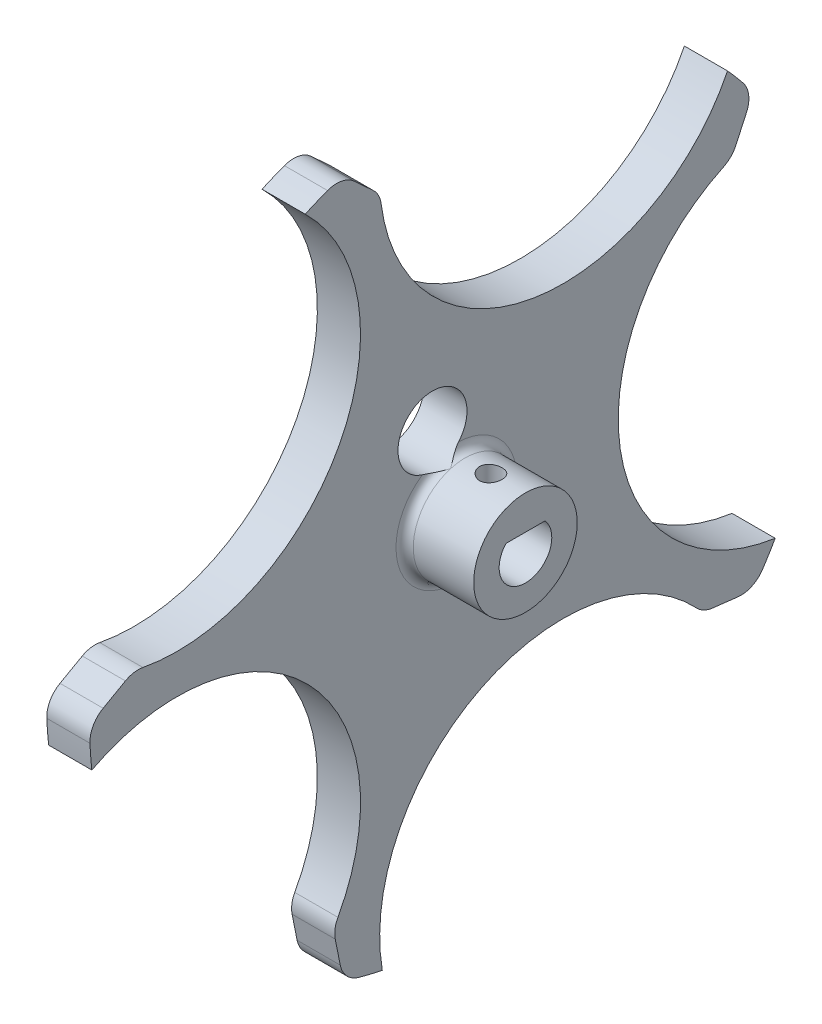
SolidWorks part; units mm, degrees
material "ABS"
ref_plane "前视基准面" through (0, 0, 0) normal (0, 0, 1) x (1, 0, 0)
ref_plane "上视基准面" through (0, 0, 0) normal (0, 1, 0) x (1, 0, 0)
ref_plane "右视基准面" through (0, 0, 0) normal (1, 0, 0) x (0, 0, -1)
ref_plane "基准面1" through (-38.0916, 0, 0) normal (-1, 0, 0) x (0, 0, 1)
sketch "草图2" plane through (-38.0916, 0, 0) normal (-1, 0, 0) x (0, 0, 1)
  line L8 (50.9114, 23.5166) -> (55.2476, 27.5126)
  line L9 (42.0845, -12.8976) -> (18.6016, -26.2672) construction
  line L10 (22.1126, 5.3045) -> (42.0845, -12.8976) construction
  line L11 (10.1802, 6.7498) -> (7.7198, 12.1087)
  line L12 (42.0845, -12.8976) -> (22.1126, 5.3045) construction
  line L13 (23.3345, -12.8976) -> (42.0845, -12.8976) construction
  line L14 (53.2241, 11.7215) -> (42.0845, -12.8976) construction
  line L15 (36.2904, 4.9347) -> (42.0845, -12.8976) construction
  line L16 (79.4441, -10.0398) -> (84.5845, -12.929)
  line L17 (42.0845, -12.8976) -> (53.2241, 11.7215) construction
  line L18 (68.941, -15.8842) -> (42.0845, -12.8976) construction
  line L19 (57.2536, -1.8766) -> (42.0845, -12.8976) construction
  line L20 (56.3471, -47.5456) -> (55.1878, -53.3272)
  line L21 (42.0845, -12.8976) -> (68.941, -15.8842) construction
  line L22 (47.5432, -39.3626) -> (42.0845, -12.8976) construction
  line L23 (57.2536, -23.9186) -> (42.0845, -12.8976) construction
  line L24 (13.5397, -37.169) -> (7.6828, -37.853)
  line L25 (42.0845, -12.8976) -> (47.5432, -39.3626) construction
  line L26 (18.6016, -26.2672) -> (42.0845, -12.8976) construction
  line L27 (36.2904, -30.7299) -> (42.0845, -12.8976) construction
  arc A41 (55.2476, 27.5126) -> (59.6047, 25.8231) centre (42.0845, -12.8976) cw
  arc A43 (7.7198, 12.1087) -> (10.673, 15.7305) centre (42.0845, -12.8976) cw
  arc A45 (10.1802, 6.7498) -> (5.1509, -33.9252) centre (2.0845, -12.8976) cw
  arc A46 (50.9114, 23.5166) -> (10.673, 15.7305) centre (29.7238, 25.1447) cw
  arc A47 (84.5845, -12.929) -> (84.3241, -17.5949) centre (42.0845, -12.8976) cw
  arc A49 (79.4441, -10.0398) -> (59.6047, 25.8231) centre (74.4452, 10.6138) cw
  arc A50 (55.1878, -53.3272) -> (50.6698, -54.5214) centre (42.0845, -12.8976) cw
  arc A52 (56.3471, -47.5456) -> (84.3241, -17.5949) centre (74.4452, -36.409) cw
  arc A53 (7.6828, -37.853) -> (5.1509, -33.9252) centre (42.0845, -12.8976) cw
  arc A55 (13.5397, -37.169) -> (50.6698, -54.5214) centre (29.7238, -50.9399) cw
  point P15 (42.0845, -12.8976)
  point P16 (42.0845, -12.8976)
  point P18 (42.0845, -12.8976)
  point P19 (42.0845, -12.8976)
  point P23 (42.0845, -12.8976)
  point P24 (42.0845, -12.8976)
  point P27 (42.0845, -12.8976)
  point P28 (42.0845, -12.8976)
  point P29 (42.0845, -12.8976)
  point P30 (42.0845, -12.8976)
  point P31 (42.0845, -12.8976)
  point P32 (42.0845, -12.8976)
  point P33 (42.0845, -12.8976)
  point P34 (42.0845, -12.8976)
  point P35 (42.0845, -12.8976)
  point P36 (42.0845, -12.8976)
  point P37 (42.0845, -12.8976)
  point P38 (42.0845, -12.8976)
  point P39 (42.0845, -12.8976)
  point P40 (42.0845, -12.8976)
  point P41 (42.0845, -12.8976)
  point P42 (42.0845, -12.8976)
  point P44 (42.0845, -12.8976)
  point P45 (42.0845, -12.8976)
  point P46 (42.0845, -12.8976)
  point P47 (42.0845, -12.8976)
  point P48 (42.0845, -12.8976)
  point P49 (42.0845, -12.8976)
  point P50 (42.0845, -12.8976)
  point P51 (42.0845, -12.8976)
  point P52 (42.0845, -12.8976)
  point P53 (42.0845, -12.8976)
  point P62 (42.0845, -12.8976)
  point P63 (42.0845, -12.8976)
  point P64 (42.0845, -12.8976)
  point P65 (42.0845, -12.8976)
  point P66 (42.0845, -12.8976)
  point P67 (42.0845, -12.8976)
  point P69 (42.0845, -12.8976)
  point P70 (42.0845, -12.8976)
  point P71 (42.0845, -12.8976)
  point P72 (42.0845, -12.8976)
  point P73 (42.0845, -12.8976)
  point P74 (42.0845, -12.8976)
  point P75 (42.0845, -12.8976)
  point P76 (42.0845, -12.8976)
  point P77 (42.0845, -12.8976)
  point P78 (42.0845, -12.8976)
  point P87 (42.0845, -12.8976)
  point P88 (42.0845, -12.8976)
  point P89 (42.0845, -12.8976)
  point P90 (42.0845, -12.8976)
  point P91 (42.0845, -12.8976)
  point P92 (42.0845, -12.8976)
  point P94 (42.0845, -12.8976)
  point P95 (42.0845, -12.8976)
  point P96 (42.0845, -12.8976)
  point P97 (42.0845, -12.8976)
  point P98 (42.0845, -12.8976)
  point P99 (42.0845, -12.8976)
  point P100 (42.0845, -12.8976)
  point P101 (42.0845, -12.8976)
  point P102 (42.0845, -12.8976)
  point P103 (42.0845, -12.8976)
  point P112 (42.0845, -12.8976)
  point P113 (42.0845, -12.8976)
  point P114 (42.0845, -12.8976)
  point P115 (42.0845, -12.8976)
  point P116 (42.0845, -12.8976)
  point P117 (42.0845, -12.8976)
  point P119 (42.0845, -12.8976)
  point P120 (42.0845, -12.8976)
  point P121 (42.0845, -12.8976)
  point P122 (42.0845, -12.8976)
  point P123 (42.0845, -12.8976)
  point P124 (42.0845, -12.8976)
  point P125 (42.0845, -12.8976)
  point P126 (42.0845, -12.8976)
  point P127 (42.0845, -12.8976)
  point P128 (42.0845, -12.8976)
  point P129 (42.0845, -12.8976)
  dimension "D1" = 5
extrude "凸台-拉伸2" add sketch "草图2" along normal mid plane 5 contours A45 L11 A43 A46 L8 A41 A49 L16 A47 A52 L20 A50 A55 L24 A53
sketch "草图4" plane through (-35.5916, 0, 0) normal (1, 0, 0) x (0, 0, -1)
  circle A0 centre (-42.0845, -12.8976) radius 6
  dimension "D1" = 12
extrude "凸台-拉伸3" add sketch "草图4" along normal blind 8
sketch "草图13" plane through (-27.5916, 0, 0) normal (1, 0, 0) x (0, 0, -1)
  line L0 (-44.3428, -10.8476) -> (-39.8262, -10.8476)
  arc A0 (-44.3428, -10.8476) -> (-39.8262, -10.8476) centre (-42.0845, -12.8976) ccw
  dimension "D1" = 6.1
  dimension "D2" = 2.05
extrude "切除-拉伸5" cut sketch "草图13" against normal blind 11.5
sketch "草图14" plane through (-40.5916, 0, 0) normal (-1, 0, 0) x (0, 0, 1)
  circle A0 centre (42.0845, -12.8976) radius 1.6
  dimension "D1" = 3.2
extrude "切除-拉伸6" cut sketch "草图14" against normal blind 12
sketch "草图15" plane through (0, -10.8476, 0) normal (0, -1, 0) x (1, 0, 0)
  line L0 (-27.5916, 36.0845) -> (-27.5916, 48.0845) construction
  circle A0 centre (-31.5916, 42.0845) radius 1.3
  dimension "D1" = 2.6
  dimension "D2" = 4
extrude "切除-拉伸7" cut sketch "草图15" against normal blind 11
fillet "圆角7" radius 1 1 edges at (-35.5916, -6.8976, 42.0845)
fillet "Fillet1" radius 3 10 edges at (-38.0916, -47.5456, 56.3471) (-38.0916, -53.3272, 55.1878) (-38.0916, -37.853, 7.6828) (-38.0916, -37.169, 13.5397) (-38.0916, 6.7498, 10.1802) (-38.0916, 12.1087, 7.7198) (-38.0916, -12.929, 84.5845) (-38.0916, -10.0398, 79.4441) (-38.0916, 27.5126, 55.2476) (-38.0916, 23.5166, 50.9114)
sketch "Sketch1" plane through (-40.5916, 0, 0) normal (-1, 0, 0) x (0, 0, 1)
  circle A15 centre (44.8569, -3.2896) radius 4
  circle A31 centre (42.0845, -12.8976) radius 1.6 construction
  point P4 (44.3472, -3.157)
  point P5 (44.8569, -3.2896)
  dimension "D1" = 10
  dimension "D2" = 8
extrude "Cut-Extrude2" cut sketch "Sketch1" against normal blind 50
